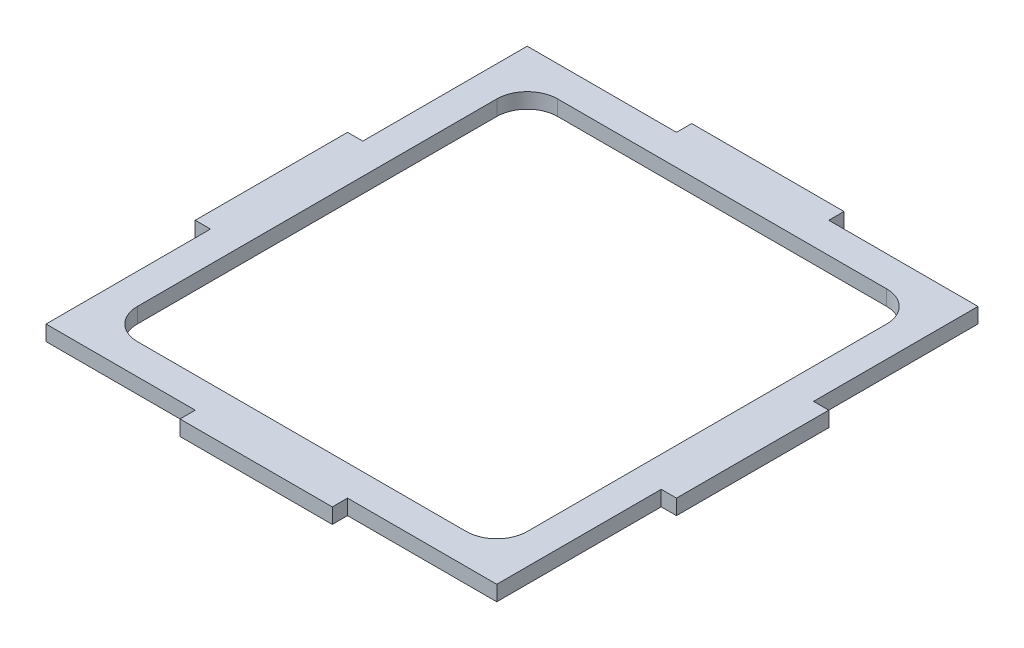
SolidWorks part; units mm, degrees
ref_plane "Front" through (0, 0, 0) normal (0, 0, 1) x (1, 0, 0)
ref_plane "Top" through (0, 0, 0) normal (0, 1, 0) x (1, 0, 0)
ref_plane "Right" through (0, 0, 0) normal (1, 0, 0) x (0, 0, -1)
sketch "Skizze1" plane through (0, 0, 0) normal (0, 1, 0) x (1, 0, 0)
  line L1 (-74, -79) -> (74, -79)
  line L2 (-74, -79) -> (-74, 79)
  line L3 (-74, 79) -> (74, 79)
  line L4 (74, -79) -> (74, 79)
  line L5 (-74, -79) -> (74, 79) construction
  line L6 (-74, 79) -> (74, -79) construction
  point P0 (0, 0)
  dimension "D1" = 148
  dimension "D2" = 158
extrude "Aufsatz-Linear austragen1" add sketch "Skizze1" along normal blind 5
sketch "Skizze2" plane through (0, 5, 0) normal (0, 1, 0) x (1, 0, 0)
  line L0 (-74, 79) -> (-74, -79) construction
  line L1 (79, -25) -> (-79, -25)
  line L2 (79, -25) -> (79, 25)
  line L3 (79, 25) -> (-79, 25)
  line L4 (-79, -25) -> (-79, 25)
  line L5 (79, -25) -> (-79, 25) construction
  line L6 (79, 25) -> (-79, -25) construction
  point P0 (0, 0)
  dimension "D1" = 5
  dimension "D2" = 50
extrude "Aufsatz-Linear austragen2" add sketch "Skizze2" against normal blind 5
ref_axis "Achse1" through (0, 50, 0) along (0, -1, 0)
sketch "Skizze3" plane through (0, 5, 0) normal (0, 1, 0) x (1, 0, 0)
  line L1 (-25, -84) -> (25, -84)
  line L2 (-25, -84) -> (-25, 84)
  line L3 (-25, 84) -> (25, 84)
  line L4 (25, -84) -> (25, 84)
  line L5 (-25, -84) -> (25, 84) construction
  line L6 (-25, 84) -> (25, -84) construction
  line L7 (-79, 25) -> (-79, -25) construction
  line L8 (-74, 79) -> (74, 79) construction
  point P8 (0, 0)
  dimension "D1" = 5
extrude "Aufsatz-Linear austragen3" add sketch "Skizze3" against normal blind 5
sketch "Skizze4" plane through (0, 5, 0) normal (0, 1, 0) x (1, 0, 0)
  circle A0 centre (0, 0) radius 50
  dimension "D1" = 100
extrude "Schnitt-Linear austragen1" cut sketch "Skizze4" against normal blind 5
sketch "Skizze5" plane through (0, 5, 0) normal (0, 1, 0) x (1, 0, 0)
  line L0 (64, -69) -> (64, 69)
  line L1 (79, -84) -> (-79, -84) construction
  line L2 (79, -84) -> (79, 84) construction
  line L3 (79, 84) -> (-79, 84) construction
  line L4 (-79, -84) -> (-79, 84) construction
  line L5 (79, -84) -> (-79, 84) construction
  line L6 (79, 84) -> (-79, -84) construction
  line L7 (64, 69) -> (-64, 69)
  line L8 (-64, -69) -> (-64, 69)
  line L9 (64, -69) -> (-64, -69)
  point P0 (0, 0)
  dimension "D1" = 15
extrude "Schnitt-Linear austragen2" cut sketch "Skizze5" against normal through all
fillet "Verrundung1" radius 10 4 edges at (-64, 2.5, 69) (64, 2.5, 69) (64, 2.5, -69) (-64, 2.5, -69)
